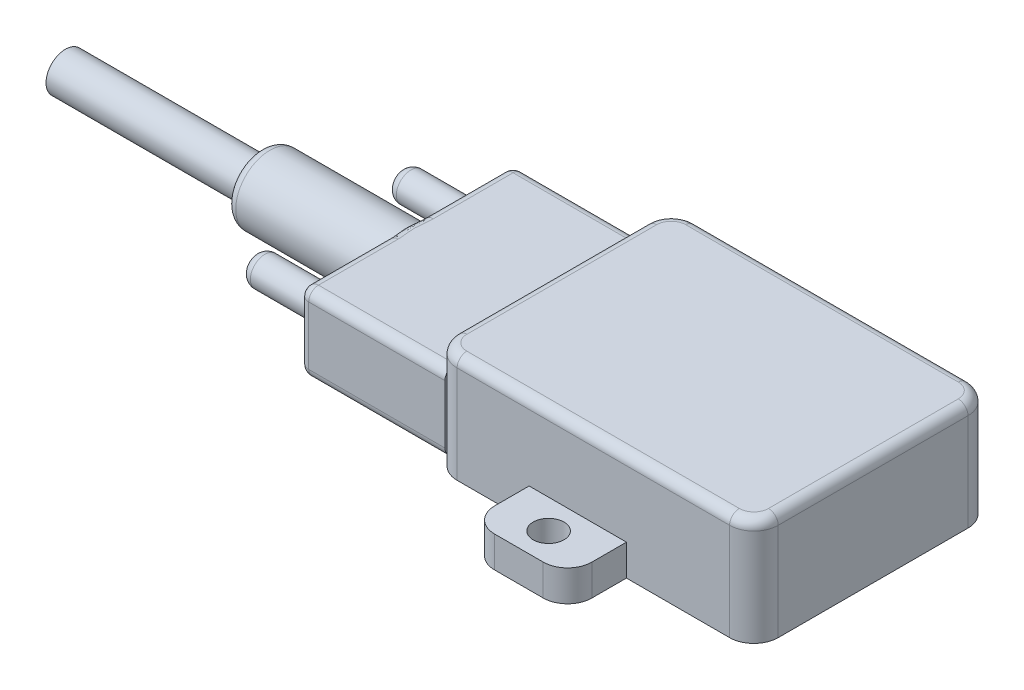
SolidWorks part; units mm, degrees
ref_plane "Ebene vorne" through (0, 0, 0) normal (0, 0, 1) x (1, 0, 0)
ref_plane "Ebene oben" through (0, 0, 0) normal (0, 1, 0) x (1, 0, 0)
ref_plane "Ebene rechts" through (0, 0, 0) normal (1, 0, 0) x (0, 0, -1)
sketch "Skizze1" plane through (0, 0, 0) normal (0, 1, 0) x (1, 0, 0)
  line L0 (0, 20.5286) -> (0, -18.2582) construction
  line L1 (-21.9159, 0) -> (25.5993, 0) construction
  line L2 (-16.5, -9.75) -> (-16.5, 9.75)
  line L3 (-14, 12.25) -> (14, 12.25)
  line L4 (16.5, -9.75) -> (16.5, 9.75)
  line L5 (-14, -12.25) -> (14, -12.25)
  arc A0 (-14, 12.25) -> (-16.5, 9.75) centre (-14, 9.75) ccw
  arc A1 (14, 12.25) -> (16.5, 9.75) centre (14, 9.75) cw
  arc A2 (14, -12.25) -> (16.5, -9.75) centre (14, -9.75) ccw
  arc A3 (-14, -12.25) -> (-16.5, -9.75) centre (-14, -9.75) cw
  point P8 (-16.5, 0)
  point P13 (0, 12.25)
  point P20 (0, -12.25)
  point P21 (16.5, 0)
  dimension "D1" = 2.5
  dimension "D2" = 33
  dimension "D3" = 24.5
extrude "Aufsatz-Linear austragen1" add sketch "Skizze1" along normal blind 11
sketch "Skizze2" plane through (0, 0, 0) normal (0, 1, 0) x (1, 0, 0)
  line L0 (-1.6, 24.8474) -> (-1.6, -21.3732) construction
  line L1 (-23.7859, 0) -> (24.4966, 0) construction
  line L2 (-6.6, -15.8) -> (-6.6, 15.8)
  line L3 (-4.1, 18.3) -> (0.9, 18.3)
  line L4 (3.4, 15.8) -> (3.4, -15.8)
  line L5 (-4.1, -18.3) -> (0.9, -18.3)
  line L7 (-16.5, 9.75) -> (-16.5, -9.75) construction
  arc A0 (3.4, -15.8) -> (0.9, -18.3) centre (0.9, -15.8) cw
  arc A1 (-4.1, -18.3) -> (-6.6, -15.8) centre (-4.1, -15.8) cw
  arc A2 (3.4, 15.8) -> (0.9, 18.3) centre (0.9, 15.8) ccw
  arc A3 (-4.1, 18.3) -> (-6.6, 15.8) centre (-4.1, 15.8) ccw
  circle A4 centre (-1.6, 15.25) radius 1.585
  circle A5 centre (-1.6, -15.25) radius 1.585
  point P10 (3.4, 0)
  point P11 (-6.6, 0)
  point P13 (3.4, -18.3)
  point P16 (-6.6, -18.3)
  point P19 (3.4, 18.3)
  point P22 (-6.6, 18.3)
  dimension "D1" = 2.5
  dimension "D6" = 3.17
  dimension "D2" = 10
  dimension "D3" = 36.6
  dimension "D4" = 14.9
  dimension "D5" = 30.5
extrude "Aufsatz-Linear austragen2" add sketch "Skizze2" along normal blind 3.2
fillet "Verrundung2" radius 1 8 edges at (0, 11, -12.25) (15.7678, 11, -11.5178) (16.5, 11, 0) (15.7678, 11, 11.5178) (0, 11, 12.25) (-15.7678, 11, 11.5178) (-16.5, 11, 0) (-15.7678, 11, -11.5178)
sketch "Skizze3" plane through (-16.5, 0, 0) normal (-1, 0, 0) x (0, 0, 1)
  line L0 (0, 24.5598) -> (0, -11.2742) construction
  line L1 (-27.9376, 0) -> (27.2724, 0) construction
  line L2 (10, 0) -> (-10, 0)
  line L3 (-11, 1) -> (-11, 7)
  line L4 (-10, 8) -> (10, 8)
  line L5 (11, 1) -> (11, 7)
  arc A0 (-10, 0) -> (-11, 1) centre (-10, 1) cw
  arc A1 (-11, 7) -> (-10, 8) centre (-10, 7) cw
  arc A2 (11, 7) -> (10, 8) centre (10, 7) ccw
  arc A3 (10, 0) -> (11, 1) centre (10, 1) ccw
  point P9 (0, 0)
  point P11 (-11, 0)
  point P20 (0, 8)
  dimension "D1" = 1
  dimension "D2" = 22
  dimension "D3" = 8
extrude "Aufsatz-Linear austragen3" add sketch "Skizze3" along normal blind 15
sketch "Skizze4" plane through (-31.5, 0, 0) normal (-1, 0, 0) x (0, 0, 1)
  line L0 (-22.166, 4) -> (24.9116, 4) construction
  line L1 (0, 20.3152) -> (0, -8.5129) construction
  line L2 (10, 8) -> (-10, 8) construction
  line L3 (-10, 0) -> (10, 0) construction
  circle A0 centre (0, 4) radius 3.5
  dimension "D1" = 7
extrude "Aufsatz-Linear austragen4" add sketch "Skizze4" along normal blind 15
sketch "Skizze5" plane through (-31.5, 0, 0) normal (-1, 0, 0) x (0, 0, 1)
  line L0 (0, 22.1782) -> (0, -12.4947) construction
  line L1 (-10, 0) -> (10, 0) construction
  line L2 (-18.6499, 4) -> (17.0302, 4) construction
  line L5 (10, 8) -> (-10, 8) construction
  circle A0 centre (-7.5, 4) radius 1.5
  circle A1 centre (7.5, 4) radius 1.5
  dimension "D1" = 3
  dimension "D2" = 15
extrude "Aufsatz-Linear austragen5" add sketch "Skizze5" along normal blind 8
sketch "Skizze6" plane through (-46.5, 0, 0) normal (-1, 0, 0) x (0, 0, 1)
  circle A0 centre (0, 4) radius 2
  dimension "D1" = 4
extrude "Aufsatz-Linear austragen6" add sketch "Skizze6" along normal blind 20
fillet "Verrundung1" radius 1 11 edges at (-31.5, 0.2929, 10.7071) (-31.5, 0, 0) (-31.5, 0.2929, -10.7071) (-31.5, 4, -11) (-31.5, 7.7071, -10.7071) (-31.5, 8, 0) (-31.5, 7.7071, 10.7071) (-39.5, 4, -6) (-39.5, 4, 6) (-46.5, 4, 3.5) (-31.5, 4, 11)
